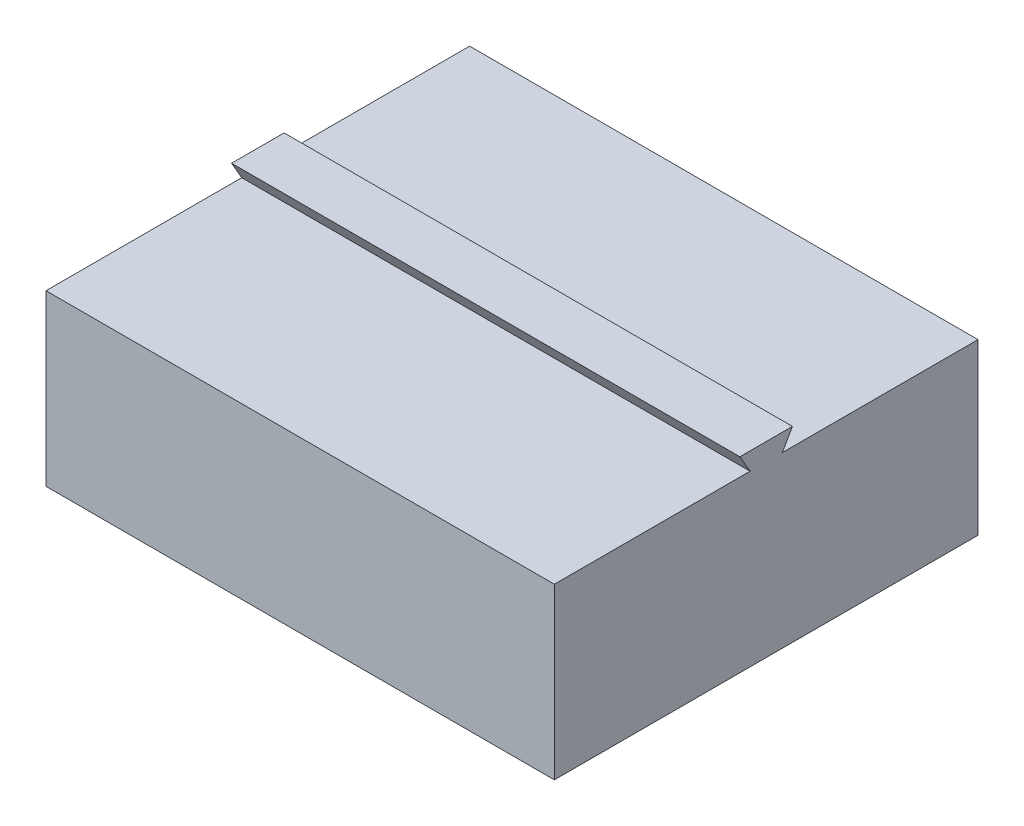
SolidWorks part; units mm, degrees
ref_plane "Front Plane" through (0, 0, 0) normal (0, 0, 1) x (1, 0, 0)
ref_plane "Top Plane" through (0, 0, 0) normal (0, 1, 0) x (1, 0, 0)
ref_plane "Right Plane" through (0, 0, 0) normal (1, 0, 0) x (0, 0, -1)
sketch "Sketch1" plane through (0, 0, 0) normal (0, 1, 0) x (1, 0, 0)
  line L1 (60, -50) -> (-60, -50)
  line L2 (60, -50) -> (60, 50)
  line L3 (60, 50) -> (-60, 50)
  line L4 (-60, -50) -> (-60, 50)
  line L5 (60, -50) -> (-60, 50) construction
  line L6 (60, 50) -> (-60, -50) construction
  point P0 (0, 0)
  dimension "D1" = 120
  dimension "D2" = 100
extrude "Boss-Extrude1" add sketch "Sketch1" along normal blind 40
sketch "Sketch2" plane through (60, 0, 0) normal (1, 0, 0) x (0, 0, -1)
  line L0 (-3.8, 40) -> (-6.2018, 44.16)
  line L1 (-50, 40) -> (50, 40) construction
  line L2 (-6.2018, 44.16) -> (6.2018, 44.16)
  line L3 (6.2018, 44.16) -> (3.8, 40)
  line L4 (3.8, 40) -> (-3.8, 40)
  line L5 (0, -1000) -> (0, 49000) construction
  dimension "D1" = 60
  dimension "D2" = 4.16
  dimension "D3" = 60
  dimension "D4" = 7.6
extrude "Boss-Extrude2" add sketch "Sketch2" against normal up to surface (120 mm away) up to face at (-60, 20, 0)
ref_point "Point1"
ref_axis "Axis1" through (0, 0, 0) along (0, 1, 0)
ref_point "Point2"
ref_axis "Axis2" through (-60, 20.229, 0) along (1, 0, 0)
ref_point "CM"
sketch "Sketch3" plane through (0, 0, 0) normal (0, -1, 0) x (1, 0, 0)
  line L0 (-60, 50) -> (60, 50) construction
  line L1 (56, -46) -> (-56, -46)
  line L2 (56, -46) -> (56, 46)
  line L3 (56, 46) -> (-56, 46)
  line L4 (-56, -46) -> (-56, 46)
  line L5 (56, -46) -> (-56, 46) construction
  line L6 (56, 46) -> (-56, -46) construction
  line L7 (60, 50) -> (60, -50) construction
  point P0 (0, 0)
  dimension "D1" = 4
  dimension "D2" = 4
sketch "Sketch5" plane through (0, 0, 0) normal (0, -1, 0) x (1, 0, 0)
  line L0 (-10.8887, -30.1351) -> (-10.8887, 13.3244)
  line L1 (-10.8887, 13.3244) -> (-25.4837, 13.3244)
  line L2 (-25.4837, 13.3244) -> (0, 40.5462)
  line L3 (0, 40.5462) -> (25.4837, 13.3244)
  line L4 (25.4837, 13.3244) -> (10.8887, 13.3244)
  line L5 (10.8887, 13.3244) -> (10.8887, -30.1351)
  line L6 (10.8887, -30.1351) -> (-10.8887, -30.1351)
  line L7 (0, -990.9816) -> (0, 49009.0184) construction
  line L8 (56, -46) -> (-56, 46) construction
  point P12 (0, 0)
extrude "Cut-Extrude2" cut sketch "Sketch5" against normal blind 1
